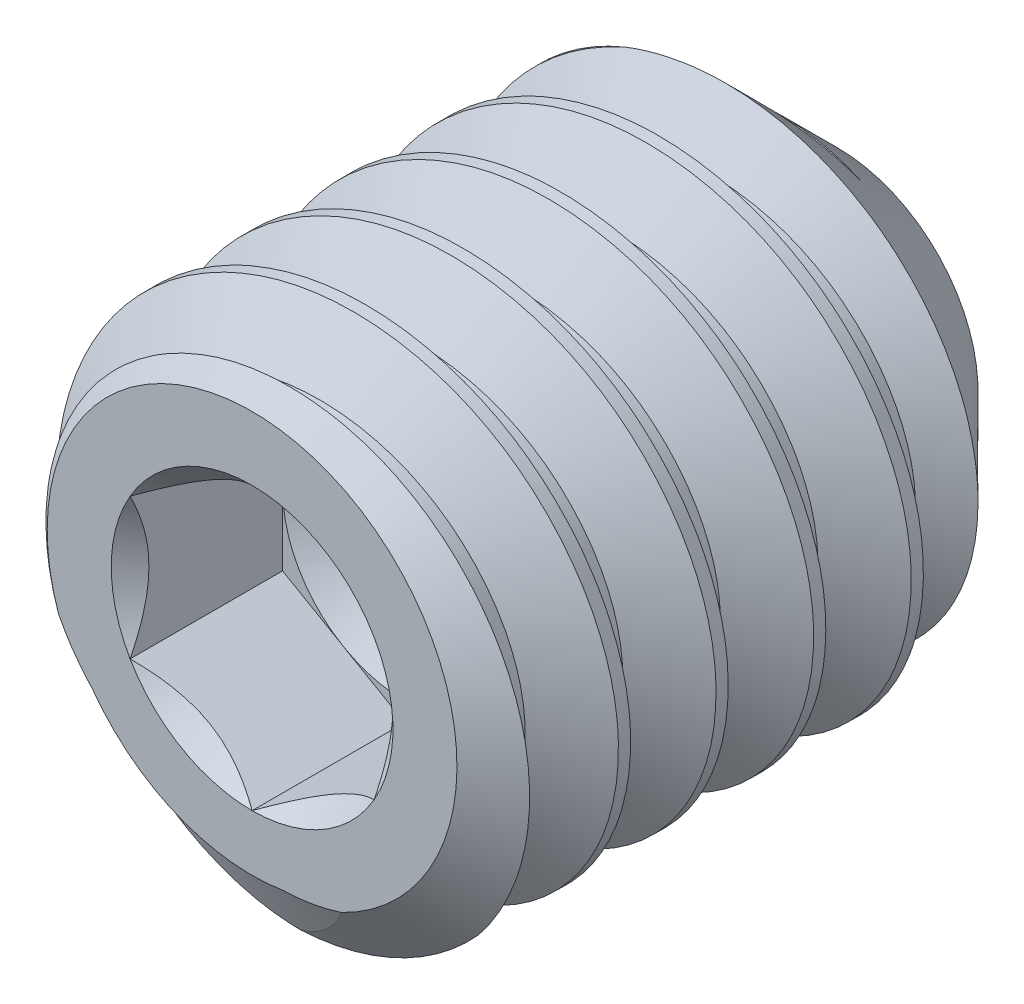
SolidWorks part; units mm, degrees
material "AISI 304"
ref_plane "Front" through (0, 0, 0) normal (0, 0, 1) x (1, 0, 0)
ref_plane "Top" through (0, 0, 0) normal (0, 1, 0) x (1, 0, 0)
ref_plane "Right" through (0, 0, 0) normal (1, 0, 0) x (0, 0, -1)
sketch "Sketch22" plane through (0, 0, 0) normal (1, 0, 0) x (0, 0, -1)
  line L0 (-2.0384, 0) -> (-2.0384, 1.6662)
  line L1 (-2.0384, 1.6662) -> (-1.7467, 2.0828)
  line L2 (-1.7467, 2.0828) -> (1.7826, 2.0828)
  line L3 (1.7826, 2.0828) -> (2.7241, 1.1413)
  line L4 (2.7241, 1.1413) -> (2.0384, 0)
  line L5 (2.0384, 0) -> (-2.0384, 0)
  line L6 (2.0384, 0) -> (2.7241, 0) construction
  line L7 (2.7241, 0) -> (2.7241, 1.1413) construction
  line L8 (2.7241, -1.1413) -> (2.0384, 0) construction
  line L9 (-1.7467, -2.0828) -> (1.7826, -2.0828) construction
  dimension "D3" = 35
  dimension "D5" = 118
  dimension "D6" = 45
  dimension "D7" = 3.3325
revolve "Revolve1" add sketch "Sketch22" angle 360 about L6
ref_plane "Plane1" through (0, 0, -2.7241) normal (0, 0, 1) x (1, 0, 0)
sketch "Sketch27" plane through (0, 0, -2.7241) normal (0, 0, 1) x (1, 0, 0)
  circle A0 centre (0, 0) radius 2.0828 construction
  circle A1 centre (0, 0) radius 2.0828
curve "Helix/Spiral1" pitch 0.7937 height 5.8103 radius 2.0828 centre (0, 0, -2.7241) axis (0, 0, 1) start towards (0, 1, 0)
sketch "Sketch28" plane through (0, 0, 0) normal (1, 0, 0) x (0, 0, -1)
  line L0 (2.7241, 2.0828) -> (3.4187, 2.0828)
  line L1 (3.4187, 2.0828) -> (3.1409, 1.6016)
  line L2 (3.1409, 1.6016) -> (3.0019, 1.6016)
  line L3 (3.0019, 1.6016) -> (2.7241, 2.0828)
  line L4 (2.863, 1.8422) -> (3.2798, 1.8422) construction
  line L6 (-1.7467, 2.0828) -> (1.7826, 2.0828) construction
  line L7 (2.7241, 2.3089) -> (2.7241, -2.3089) construction
  dimension "D1" = 0.1389
  dimension "D3" = 60
  dimension "D2" = 0.6945
sweep "Cut-Sweep2" cut profiles "Sketch28" path "Helix/Spiral1" align with end faces yes
sketch "Sketch23" plane through (0, 0, 2.0384) normal (0, 0, 1) x (1, 0, 0)
  line L1 (0, 1.1457) -> (-0.9922, 0.5728)
  line L2 (-0.9922, 0.5728) -> (-0.9922, -0.5728)
  line L3 (-0.9922, -0.5728) -> (0, -1.1457)
  line L4 (0, -1.1457) -> (0.9922, -0.5728)
  line L5 (0.9922, -0.5728) -> (0.9922, 0.5728)
  line L6 (0.9922, 0.5728) -> (0, 1.1457)
  circle A0 centre (0, 0) radius 0.9922 construction
extrude "Cut-Extrude10" cut sketch "Sketch23" against normal blind 1.2402
sketch "Sketch24" plane through (0, 0, 2.0384) normal (0, 0, 1) x (1, 0, 0)
  circle A0 centre (0, 0) radius 1.1457
extrude "Cut-Extrude11" cut sketch "Sketch24" against normal through all draft 45
sketch "Sketch26" plane through (0, 0, 0.7981) normal (0, 0, 1) x (1, 0, 0)
  circle A0 centre (0, 0) radius 0.9922 construction
  circle A1 centre (0, 0) radius 0.9922
extrude "Cut-Extrude12" cut sketch "Sketch26" against normal through all draft 60
sketch "Sketch30" plane through (0, 0, 0) normal (1, 0, 0) x (0, 0, -1)
  line L0 (-1.7467, 2.0828) -> (1.7826, 2.0828) construction
  line L1 (-2.0384, 0) -> (-2.0384, 1.6662) construction
  line L2 (2.7241, 0) -> (2.7241, 1.1413) construction
  line L3 (-1.7467, -2.0828) -> (1.7826, -2.0828) construction
  point P0 (-2.0384, 2.0828)
  point P1 (2.7241, 2.0828)
  point P2 (2.7241, -2.0828)
  point P11 (0.7398, -2.0828)
  dimension "D1" = 1.9844
sketch "Sketch31" plane through (0, 0, 0) normal (1, 0, 0) x (0, 0, -1)
  line L2 (2.0384, 0) -> (2.7241, -1.1413)
  line L3 (2.7241, 1.1413) -> (2.0384, 0)
ref_plane "Plane2" through (0, 0, -2.7241) normal (0, 0, -1) x (-1, 0, 0)
ref_axis "Axis1" through (0, 0, -4.2916) along (0, 0, 1)
equation "\"D7@Sketch22\"=\"Dia@Sketch22\"*.8"
equation "\"D1@Sketch28\" = \"D4@Helix/Spiral1\" * .175"
equation "\"D3@Helix/Spiral1\" = \"Length@Sketch22\" + \"D4@Helix/Spiral1\" + .01"
equation "\"D1@Sketch30\" = \"D4@Helix/Spiral1\" * 2.5"
equation "\"hex Depth@Cut-Extrude10\" = \"Hex@Sketch23\" * .625"
equation "\"D2@Sketch28\" = \"D4@Helix/Spiral1\" * .875"
